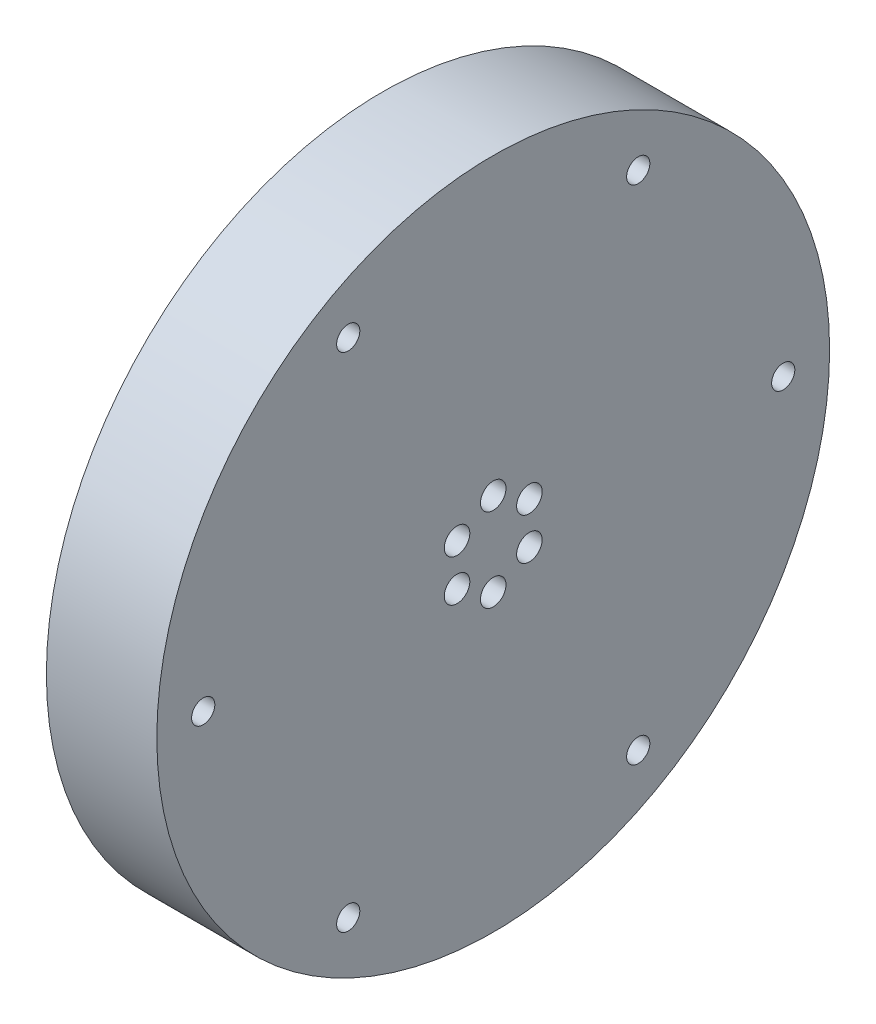
SolidWorks part; units mm, degrees
ref_plane "Front Plane" through (0, 0, 0) normal (0, 0, 1) x (1, 0, 0)
ref_plane "Top Plane" through (0, 0, 0) normal (0, 1, 0) x (1, 0, 0)
ref_plane "Right Plane" through (0, 0, 0) normal (1, 0, 0) x (0, 0, -1)
sketch "Sketch1" plane through (0, 0, 0) normal (1, 0, 0) x (0, 0, -1)
  circle A0 centre (0, 0) radius 12.5
  circle A1 centre (0, 0) radius 37.75
  circle A2 centre (0, 0) radius 49.75
  circle A3 centre (0, 0) radius 67.525
  circle A4 centre (0, 0) radius 72.5
  dimension "D1" = 145
  dimension "D2" = 135.05
  dimension "D3" = 99.5
  dimension "D4" = 75.5
  dimension "D5" = 25
extrude "Boss-Extrude1" add sketch "Sketch1" along normal blind 10 contours A4
extrude "Boss-Extrude2" add sketch "Sketch1<3>" against normal blind 11.55 contours A0 region at (0, 0, 0)
sketch "Sketch1<3>" plane through (0, 0, 0) normal (1, 0, 0) x (0, 0, -1) same geometry as "Sketch1"
extrude "Boss-Extrude3" add sketch "Sketch1<4>" against normal blind 6 contours A2 A1 region at (0, 0, 48.3429)
sketch "Sketch1<4>" plane through (0, 0, 0) normal (1, 0, 0) x (0, 0, -1) same geometry as "Sketch1"
extrude "Boss-Extrude4" add sketch "Sketch1<5>" against normal blind 13.8 contours A4 A3 region at (0, 0, 70.4494)
sketch "Sketch1<5>" plane through (0, 0, 0) normal (1, 0, 0) x (0, 0, -1) same geometry as "Sketch1"
sketch "Sketch2" plane through (-11.55, 0, 0) normal (-1, 0, 0) x (0, 0, 1)
  circle A0 centre (0, 0) radius 9 construction
  circle A1 centre (0, 9) radius 2.75
  circle A2 centre (7.7942, 4.5) radius 2.75
  circle A3 centre (7.7942, -4.5) radius 2.75
  circle A4 centre (0, -9) radius 2.75
  circle A5 centre (-7.7942, -4.5) radius 2.75
  circle A6 centre (-7.7942, 4.5) radius 2.75
  point P18 (0, 0)
  dimension "D1" = 18
  dimension "D2" = 5.5
  dimension "D3" = 6
extrude "Cut-Extrude1" cut sketch "Sketch2" against normal up to next from offset 5 offset against normal yes
hole_wizard "M3 Tapped Hole1" positions "Sketch3" profile "Sketch5" tap size "M3" standard "ISO" end condition through all
sketch "Sketch3" plane through (-11.55, 0, 0) normal (-1, 0, 0) x (0, 0, 1)
  circle A0 centre (0, 0) radius 9 construction
  point P0 (0, 9)
  point P14 (7.7942, 4.5)
  point P15 (7.7942, -4.5)
  point P16 (0, -9)
  point P17 (-7.7942, -4.5)
  point P18 (-7.7942, 4.5)
  dimension "D1" = 18
  dimension "D2" = 6
sketch "Sketch5" plane through (-11.55, 9, 0) normal (0, 1, 0) x (0, 0, 1)
  line L0 (0, 0) -> (0, 21.55)
  line L1 (0, 21.55) -> (1.25, 21.55)
  line L2 (1.25, 21.55) -> (1.25, 0.275)
  line L3 (1.25, 0.275) -> (1.525, 0)
  line L5 (1.525, 0) -> (0, 0)
  line L6 (-1.25, 0.275) -> (-1.525, 0) construction
  line L11 (0, -6.35) -> (0, 107.95) construction
  dimension "Thru Tap Drill Dia." = 2.5
  dimension "Thru Tap Drill Depth" = 21.55
  dimension "Near C'Sink Dia." = 3.05
  dimension "Near C'Sink Angle" = 90
cosmetic thread "Hole Thread1" parameters "D2"=3
cosmetic thread "Hole Thread2" parameters "D2"=3
cosmetic thread "Hole Thread3" parameters "D2"=3
cosmetic thread "Hole Thread4" parameters "D2"=3
cosmetic thread "Hole Thread5" parameters "D2"=3
cosmetic thread "Hole Thread6" parameters "D2"=3
sketch "Sketch6" plane through (10, 0, 0) normal (1, 0, 0) x (0, 0, -1)
  line L0 (0, 0) -> (0, 50000) construction
  circle A0 centre (0, 0) radius 62.5 construction
  circle A6 centre (-62.5, 0) radius 2.5
  circle A8 centre (-31.25, 54.1266) radius 2.5
  circle A9 centre (31.25, 54.1266) radius 2.5
  circle A10 centre (62.5, 0) radius 2.5
  circle A11 centre (31.25, -54.1266) radius 2.5
  circle A12 centre (-31.25, -54.1266) radius 2.5
  point P20 (0, 0)
  dimension "D1" = 125
  dimension "D2" = 5
  dimension "D3" = 6
extrude "Cut-Extrude2" cut sketch "Sketch6" against normal blind 6
